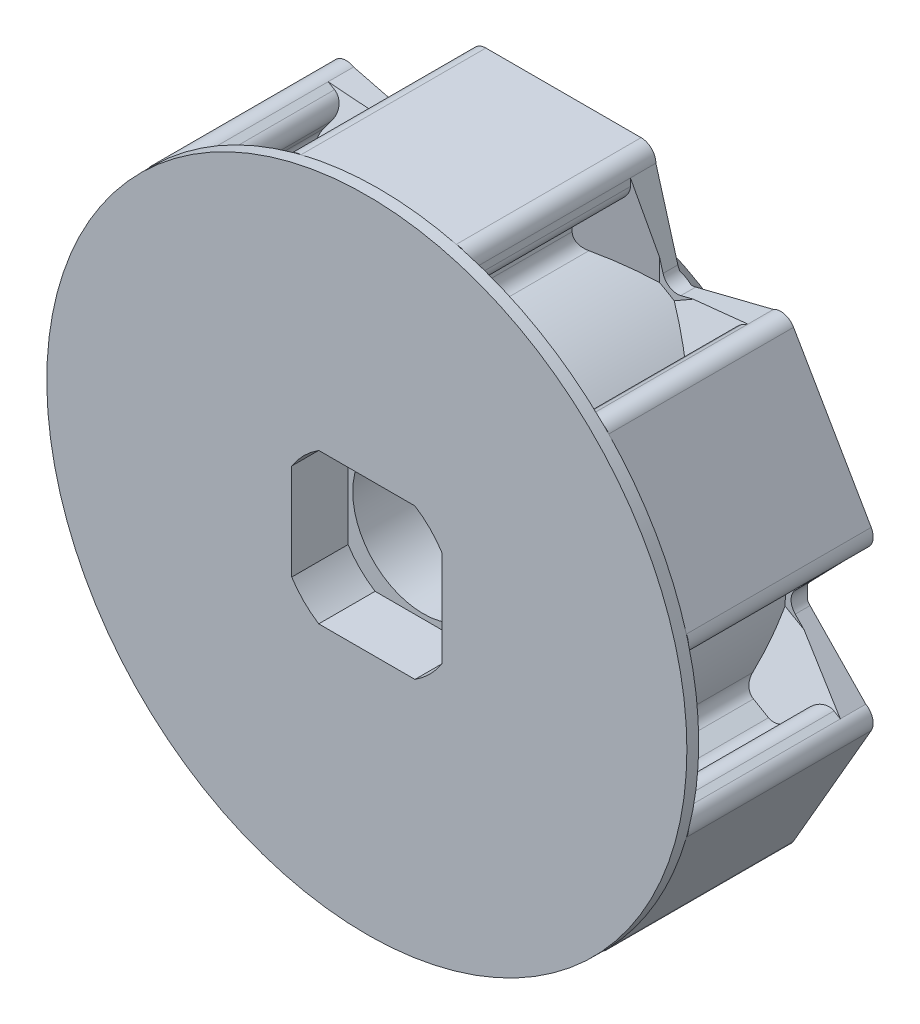
SolidWorks part; units mm, degrees
material "PE High Density"
ref_plane "Front Plane" through (0, 0, 0) normal (0, 0, 1) x (1, 0, 0)
ref_plane "Top Plane" through (0, 0, 0) normal (0, 1, 0) x (1, 0, 0)
ref_plane "Right Plane" through (0, 0, 0) normal (1, 0, 0) x (0, 0, -1)
sketch "Sketch1" plane through (0, 0, 0) normal (0, 0, 1) x (1, 0, 0)
  circle A0 centre (0, 0) radius 32
  circle A1 centre (0, 0) radius 9.525
  circle A2 centre (0, 0) radius 50 construction
  dimension "D1" = 64
  dimension "D2" = 19.05
  dimension "D3" = 100
extrude "Boss-Extrude1" add sketch "Sketch1" along normal blind 23
sketch "Sketch3" plane through (0, 0, 0) normal (0, 0, -1) x (-1, 0, 0)
  line L1 (-12.5, 42) -> (12.5, 42)
  line L2 (-12.5, 42) -> (-12.5, 37)
  line L3 (-12.5, 37) -> (12.5, 37)
  line L4 (12.5, 42) -> (12.5, 37)
  line L5 (-12.5, 42) -> (12.5, 37) construction
  line L6 (-12.5, 37) -> (12.5, 42) construction
  line L7 (7.5, 31.1087) -> (-7.5, 31.1087)
  line L8 (7.5, 31.1087) -> (7.5, 37)
  line L9 (7.5, 37) -> (-7.5, 37)
  line L10 (-7.5, 31.1087) -> (-7.5, 37)
  line L11 (7.5, 31.1087) -> (-7.5, 37) construction
  line L12 (7.5, 37) -> (-7.5, 31.1087) construction
  circle A0 centre (0, 0) radius 32 construction
  circle A1 centre (0, 0) radius 50 construction
  point P0 (0, 39.5)
  point P5 (0, 34.0543)
  dimension "D1" = 100
  dimension "D2" = 15
  dimension "D3" = 25
  dimension "D4" = 5
  dimension "D5" = 42
extrude "Boss-Extrude2" add sketch "Sketch3" against normal up to surface (23 mm away) contours L2 L1 L4 L3 | L8 L7 L10 L9 up to face at (32, 0, 23)
fillet "Fillet1" radius 2 8 edges at (7.5, 31.1087, 11.5) (7.5, 37, 11.5) (12.5, 37, 11.5) (12.5, 42, 11.5) (-12.5, 42, 11.5) (-12.5, 37, 11.5) (-7.5, 37, 11.5) (-7.5, 31.1087, 11.5)
sketch "Sketch5" plane through (0, 42, 0) normal (0, 1, 0) x (1, 0, 0)
  line L0 (10.5, 0) -> (-10.5, 0) construction
  circle A0 centre (0, -11.9253) radius 2.5
  dimension "D1" = 5
  dimension "D2" = 11.9253
pattern_circular "CirPattern1" count 6 over 360 about axis through (0, 0, 0) along (0, 0, 1) of "Boss-Extrude2", "Fillet1"
sketch "Sketch2" plane through (0, 0, 23) normal (0, 0, 1) x (1, 0, 0)
  line L1 (-10.16, -10.16) -> (10.16, -10.16)
  line L2 (-10.16, -10.16) -> (-10.16, 10.16)
  line L3 (-10.16, 10.16) -> (10.16, 10.16)
  line L4 (10.16, -10.16) -> (10.16, 10.16)
  line L5 (-10.16, -10.16) -> (10.16, 10.16) construction
  line L6 (-10.16, 10.16) -> (10.16, -10.16) construction
  arc A0 (6.5068, 10.16) -> (10.16, 6.5068) centre (0, 0) cw
  arc A1 (-6.5068, 10.16) -> (-10.16, 6.5068) centre (0, 0) ccw
  arc A2 (-10.16, -6.5068) -> (-6.5068, -10.16) centre (0, 0) ccw
  arc A3 (6.5068, -10.16) -> (10.16, -6.5068) centre (0, 0) ccw
  point P0 (0, 0)
  dimension "D1" = 20.32
extrude "Cut-Extrude2" cut sketch "Sketch2" against normal blind 6.02 contours L1 A3 L4 A0 L3 A1 L2 A2
sketch "Sketch7" plane through (0, 0, 23) normal (0, 0, 1) x (1, 0, 0)
  line L35 (36.7929, 10.2728) -> (37.2929, 9.4067)
  line L37 (36.7929, 10.2728) -> (37.2929, 9.4067)
  line L39 (40.025, 8.6747) -> (40.891, 9.1747)
  line L41 (40.025, 8.6747) -> (40.891, 9.1747)
  line L43 (41.6231, 11.9067) -> (31.1231, 30.0933)
  line L45 (41.6231, 11.9067) -> (31.1231, 30.0933)
  line L47 (28.391, 30.8253) -> (27.525, 30.3253)
  line L48 (7.5, 32.6458) -> (7.5, 35)
  line L49 (9.5, 37) -> (10.5, 37)
  line L50 (12.5, 39) -> (12.5, 40)
  line L51 (10.5, 42) -> (-10.5, 42)
  line L52 (-12.5, 40) -> (-12.5, 39)
  line L53 (-10.5, 37) -> (-9.5, 37)
  line L54 (-7.5, 35) -> (-7.5, 32.6458)
  line L56 (28.391, 30.8253) -> (27.525, 30.3253)
  line L58 (26.7929, 27.5933) -> (27.2929, 26.7272)
  line L60 (26.7929, 27.5933) -> (27.2929, 26.7272)
  line L62 (26.5609, 23.9952) -> (24.5221, 22.8181)
  line L64 (26.5609, 23.9952) -> (24.5221, 22.8181)
  line L66 (-24.5221, 22.8181) -> (-26.5609, 23.9952)
  line L68 (-24.5221, 22.8181) -> (-26.5609, 23.9952)
  line L70 (-27.2929, 26.7272) -> (-26.7929, 27.5933)
  line L72 (-27.2929, 26.7272) -> (-26.7929, 27.5933)
  line L74 (-27.525, 30.3253) -> (-28.391, 30.8253)
  line L76 (-27.525, 30.3253) -> (-28.391, 30.8253)
  line L78 (-31.1231, 30.0933) -> (-41.6231, 11.9067)
  line L80 (-31.1231, 30.0933) -> (-41.6231, 11.9067)
  line L82 (-40.891, 9.1747) -> (-40.025, 8.6747)
  line L90 (7.5, 32.6458) -> (7.5, 35)
  line L91 (9.5, 37) -> (10.5, 37)
  line L92 (12.5, 39) -> (12.5, 40)
  line L93 (10.5, 42) -> (-10.5, 42)
  line L94 (-12.5, 40) -> (-12.5, 39)
  line L95 (-10.5, 37) -> (-9.5, 37)
  line L96 (-7.5, 35) -> (-7.5, 32.6458)
  line L126 (-40.891, 9.1747) -> (-40.025, 8.6747)
  line L128 (-37.2929, 9.4067) -> (-36.7929, 10.2728)
  line L130 (-37.2929, 9.4067) -> (-36.7929, 10.2728)
  line L132 (-34.0609, 11.0048) -> (-32.0221, 9.8277)
  line L134 (-34.0609, 11.0048) -> (-32.0221, 9.8277)
  line L136 (-32.0221, -9.8277) -> (-34.0609, -11.0048)
  line L138 (-32.0221, -9.8277) -> (-34.0609, -11.0048)
  line L147 (-36.7929, -10.2728) -> (-37.2929, -9.4067)
  line L148 (-36.7929, -10.2728) -> (-37.2929, -9.4067)
  line L149 (-40.025, -8.6747) -> (-40.891, -9.1747)
  line L150 (-40.025, -8.6747) -> (-40.891, -9.1747)
  line L151 (-41.6231, -11.9067) -> (-31.1231, -30.0933)
  line L152 (-41.6231, -11.9067) -> (-31.1231, -30.0933)
  line L153 (-28.391, -30.8253) -> (-27.525, -30.3253)
  line L154 (-28.391, -30.8253) -> (-27.525, -30.3253)
  line L155 (-26.7929, -27.5933) -> (-27.2929, -26.7272)
  line L156 (-26.7929, -27.5933) -> (-27.2929, -26.7272)
  line L157 (-26.5609, -23.9952) -> (-24.5221, -22.8181)
  line L158 (-26.5609, -23.9952) -> (-24.5221, -22.8181)
  line L159 (-7.5, -32.6458) -> (-7.5, -35)
  line L160 (-7.5, -32.6458) -> (-7.5, -35)
  line L161 (-9.5, -37) -> (-10.5, -37)
  line L162 (-9.5, -37) -> (-10.5, -37)
  line L163 (-12.5, -39) -> (-12.5, -40)
  line L164 (-12.5, -39) -> (-12.5, -40)
  line L165 (-10.5, -42) -> (10.5, -42)
  line L166 (-10.5, -42) -> (10.5, -42)
  line L167 (12.5, -40) -> (12.5, -39)
  line L168 (12.5, -40) -> (12.5, -39)
  line L169 (10.5, -37) -> (9.5, -37)
  line L170 (10.5, -37) -> (9.5, -37)
  line L171 (7.5, -35) -> (7.5, -32.6458)
  line L172 (7.5, -35) -> (7.5, -32.6458)
  line L173 (24.5221, -22.8181) -> (26.5609, -23.9952)
  line L174 (24.5221, -22.8181) -> (26.5609, -23.9952)
  line L175 (27.2929, -26.7272) -> (26.7929, -27.5933)
  line L176 (27.2929, -26.7272) -> (26.7929, -27.5933)
  line L177 (27.525, -30.3253) -> (28.391, -30.8253)
  line L178 (27.525, -30.3253) -> (28.391, -30.8253)
  line L179 (31.1231, -30.0933) -> (41.6231, -11.9067)
  line L180 (31.1231, -30.0933) -> (41.6231, -11.9067)
  line L181 (40.891, -9.1747) -> (40.025, -8.6747)
  line L182 (40.891, -9.1747) -> (40.025, -8.6747)
  line L183 (37.2929, -9.4067) -> (36.7929, -10.2728)
  line L184 (37.2929, -9.4067) -> (36.7929, -10.2728)
  line L185 (34.0609, -11.0048) -> (32.0221, -9.8277)
  line L186 (34.0609, -11.0048) -> (32.0221, -9.8277)
  line L187 (32.0221, 9.8277) -> (34.0609, 11.0048)
  line L188 (32.0221, 9.8277) -> (34.0609, 11.0048)
  circle A0 centre (0, 0) radius 50
  arc A46 (37.2929, 9.4067) -> (40.025, 8.6747) centre (39.025, 10.4067) ccw
  arc A48 (37.2929, 9.4067) -> (40.025, 8.6747) centre (39.025, 10.4067) ccw
  arc A50 (40.891, 9.1747) -> (41.6231, 11.9067) centre (39.891, 10.9067) ccw
  arc A52 (40.891, 9.1747) -> (41.6231, 11.9067) centre (39.891, 10.9067) ccw
  arc A54 (31.1231, 30.0933) -> (28.391, 30.8253) centre (29.391, 29.0933) ccw
  arc A56 (31.1231, 30.0933) -> (28.391, 30.8253) centre (29.391, 29.0933) ccw
  arc A58 (27.525, 30.3253) -> (26.7929, 27.5933) centre (28.525, 28.5933) ccw
  arc A60 (22.1385, 23.106) -> (8.9412, 30.7255) centre (0, 0) ccw
  arc A61 (7.5, 32.6458) -> (8.9412, 30.7255) centre (9.5, 32.6458) ccw
  arc A62 (9.5, 37) -> (7.5, 35) centre (9.5, 35) ccw
  arc A63 (10.5, 37) -> (12.5, 39) centre (10.5, 39) ccw
  arc A64 (12.5, 40) -> (10.5, 42) centre (10.5, 40) ccw
  arc A65 (-10.5, 42) -> (-12.5, 40) centre (-10.5, 40) ccw
  arc A66 (-12.5, 39) -> (-10.5, 37) centre (-10.5, 39) ccw
  arc A67 (-7.5, 35) -> (-9.5, 37) centre (-9.5, 35) ccw
  arc A68 (-8.9412, 30.7255) -> (-7.5, 32.6458) centre (-9.5, 32.6458) ccw
  arc A69 (-8.9412, 30.7255) -> (-22.1385, 23.106) centre (0, 0) ccw
  arc A70 (27.525, 30.3253) -> (26.7929, 27.5933) centre (28.525, 28.5933) ccw
  arc A72 (26.5609, 23.9952) -> (27.2929, 26.7272) centre (25.5609, 25.7272) ccw
  arc A74 (26.5609, 23.9952) -> (27.2929, 26.7272) centre (25.5609, 25.7272) ccw
  arc A76 (22.1385, 23.106) -> (24.5221, 22.8181) centre (23.5221, 24.5502) ccw
  arc A78 (22.1385, 23.106) -> (24.5221, 22.8181) centre (23.5221, 24.5502) ccw
  arc A80 (-24.5221, 22.8181) -> (-22.1385, 23.106) centre (-23.5221, 24.5502) ccw
  arc A82 (-24.5221, 22.8181) -> (-22.1385, 23.106) centre (-23.5221, 24.5502) ccw
  arc A84 (-27.2929, 26.7272) -> (-26.5609, 23.9952) centre (-25.5609, 25.7272) ccw
  arc A86 (-27.2929, 26.7272) -> (-26.5609, 23.9952) centre (-25.5609, 25.7272) ccw
  arc A87 (-22.1385, -23.106) -> (-8.9412, -30.7255) centre (0, 0) ccw
  arc A89 (-26.7929, 27.5933) -> (-27.525, 30.3253) centre (-28.525, 28.5933) ccw
  arc A91 (-26.7929, 27.5933) -> (-27.525, 30.3253) centre (-28.525, 28.5933) ccw
  arc A93 (-28.391, 30.8253) -> (-31.1231, 30.0933) centre (-29.391, 29.0933) ccw
  arc A95 (-28.391, 30.8253) -> (-31.1231, 30.0933) centre (-29.391, 29.0933) ccw
  arc A96 (8.9412, -30.7255) -> (22.1385, -23.106) centre (0, 0) ccw
  arc A98 (-41.6231, 11.9067) -> (-40.891, 9.1747) centre (-39.891, 10.9067) ccw
  arc A100 (-41.6231, 11.9067) -> (-40.891, 9.1747) centre (-39.891, 10.9067) ccw
  arc A102 (-40.025, 8.6747) -> (-37.2929, 9.4067) centre (-39.025, 10.4067) ccw
  arc A104 (-40.025, 8.6747) -> (-37.2929, 9.4067) centre (-39.025, 10.4067) ccw
  arc A105 (31.0796, -7.6195) -> (31.0796, 7.6195) centre (0, 0) ccw
  arc A107 (-34.0609, 11.0048) -> (-36.7929, 10.2728) centre (-35.0609, 9.2728) ccw
  arc A114 (22.1385, 23.106) -> (8.9412, 30.7255) centre (0, 0) ccw
  arc A115 (7.5, 32.6458) -> (8.9412, 30.7255) centre (9.5, 32.6458) ccw
  arc A116 (9.5, 37) -> (7.5, 35) centre (9.5, 35) ccw
  arc A117 (10.5, 37) -> (12.5, 39) centre (10.5, 39) ccw
  arc A118 (12.5, 40) -> (10.5, 42) centre (10.5, 40) ccw
  arc A119 (-10.5, 42) -> (-12.5, 40) centre (-10.5, 40) ccw
  arc A120 (-12.5, 39) -> (-10.5, 37) centre (-10.5, 39) ccw
  arc A121 (-7.5, 35) -> (-9.5, 37) centre (-9.5, 35) ccw
  arc A122 (-8.9412, 30.7255) -> (-7.5, 32.6458) centre (-9.5, 32.6458) ccw
  arc A123 (-8.9412, 30.7255) -> (-22.1385, 23.106) centre (0, 0) ccw
  arc A141 (-22.1385, -23.106) -> (-8.9412, -30.7255) centre (0, 0) ccw
  arc A150 (8.9412, -30.7255) -> (22.1385, -23.106) centre (0, 0) ccw
  arc A159 (31.0796, -7.6195) -> (31.0796, 7.6195) centre (0, 0) ccw
  arc A163 (-34.0609, 11.0048) -> (-36.7929, 10.2728) centre (-35.0609, 9.2728) ccw
  arc A165 (-31.0796, 7.6195) -> (-32.0221, 9.8277) centre (-33.0221, 8.0957) ccw
  arc A167 (-31.0796, 7.6195) -> (-32.0221, 9.8277) centre (-33.0221, 8.0957) ccw
  arc A169 (-31.0796, 7.6195) -> (-31.0796, -7.6195) centre (0, 0) ccw
  arc A171 (-31.0796, 7.6195) -> (-31.0796, -7.6195) centre (0, 0) ccw
  arc A173 (-32.0221, -9.8277) -> (-31.0796, -7.6195) centre (-33.0221, -8.0957) ccw
  arc A175 (-32.0221, -9.8277) -> (-31.0796, -7.6195) centre (-33.0221, -8.0957) ccw
  arc A186 (-36.7929, -10.2728) -> (-34.0609, -11.0048) centre (-35.0609, -9.2728) ccw
  arc A187 (-36.7929, -10.2728) -> (-34.0609, -11.0048) centre (-35.0609, -9.2728) ccw
  arc A188 (-37.2929, -9.4067) -> (-40.025, -8.6747) centre (-39.025, -10.4067) ccw
  arc A189 (-37.2929, -9.4067) -> (-40.025, -8.6747) centre (-39.025, -10.4067) ccw
  arc A190 (-40.891, -9.1747) -> (-41.6231, -11.9067) centre (-39.891, -10.9067) ccw
  arc A191 (-40.891, -9.1747) -> (-41.6231, -11.9067) centre (-39.891, -10.9067) ccw
  arc A192 (-31.1231, -30.0933) -> (-28.391, -30.8253) centre (-29.391, -29.0933) ccw
  arc A193 (-31.1231, -30.0933) -> (-28.391, -30.8253) centre (-29.391, -29.0933) ccw
  arc A194 (-27.525, -30.3253) -> (-26.7929, -27.5933) centre (-28.525, -28.5933) ccw
  arc A195 (-27.525, -30.3253) -> (-26.7929, -27.5933) centre (-28.525, -28.5933) ccw
  arc A196 (-26.5609, -23.9952) -> (-27.2929, -26.7272) centre (-25.5609, -25.7272) ccw
  arc A197 (-26.5609, -23.9952) -> (-27.2929, -26.7272) centre (-25.5609, -25.7272) ccw
  arc A198 (-22.1385, -23.106) -> (-24.5221, -22.8181) centre (-23.5221, -24.5502) ccw
  arc A199 (-22.1385, -23.106) -> (-24.5221, -22.8181) centre (-23.5221, -24.5502) ccw
  arc A200 (-7.5, -32.6458) -> (-8.9412, -30.7255) centre (-9.5, -32.6458) ccw
  arc A201 (-7.5, -32.6458) -> (-8.9412, -30.7255) centre (-9.5, -32.6458) ccw
  arc A202 (-9.5, -37) -> (-7.5, -35) centre (-9.5, -35) ccw
  arc A203 (-9.5, -37) -> (-7.5, -35) centre (-9.5, -35) ccw
  arc A204 (-10.5, -37) -> (-12.5, -39) centre (-10.5, -39) ccw
  arc A205 (-10.5, -37) -> (-12.5, -39) centre (-10.5, -39) ccw
  arc A206 (-12.5, -40) -> (-10.5, -42) centre (-10.5, -40) ccw
  arc A207 (-12.5, -40) -> (-10.5, -42) centre (-10.5, -40) ccw
  arc A208 (10.5, -42) -> (12.5, -40) centre (10.5, -40) ccw
  arc A209 (10.5, -42) -> (12.5, -40) centre (10.5, -40) ccw
  arc A210 (12.5, -39) -> (10.5, -37) centre (10.5, -39) ccw
  arc A211 (12.5, -39) -> (10.5, -37) centre (10.5, -39) ccw
  arc A212 (7.5, -35) -> (9.5, -37) centre (9.5, -35) ccw
  arc A213 (7.5, -35) -> (9.5, -37) centre (9.5, -35) ccw
  arc A214 (8.9412, -30.7255) -> (7.5, -32.6458) centre (9.5, -32.6458) ccw
  arc A215 (8.9412, -30.7255) -> (7.5, -32.6458) centre (9.5, -32.6458) ccw
  arc A216 (24.5221, -22.8181) -> (22.1385, -23.106) centre (23.5221, -24.5502) ccw
  arc A217 (24.5221, -22.8181) -> (22.1385, -23.106) centre (23.5221, -24.5502) ccw
  arc A218 (27.2929, -26.7272) -> (26.5609, -23.9952) centre (25.5609, -25.7272) ccw
  arc A219 (27.2929, -26.7272) -> (26.5609, -23.9952) centre (25.5609, -25.7272) ccw
  arc A220 (26.7929, -27.5933) -> (27.525, -30.3253) centre (28.525, -28.5933) ccw
  arc A221 (26.7929, -27.5933) -> (27.525, -30.3253) centre (28.525, -28.5933) ccw
  arc A222 (28.391, -30.8253) -> (31.1231, -30.0933) centre (29.391, -29.0933) ccw
  arc A223 (28.391, -30.8253) -> (31.1231, -30.0933) centre (29.391, -29.0933) ccw
  arc A224 (41.6231, -11.9067) -> (40.891, -9.1747) centre (39.891, -10.9067) ccw
  arc A225 (41.6231, -11.9067) -> (40.891, -9.1747) centre (39.891, -10.9067) ccw
  arc A226 (40.025, -8.6747) -> (37.2929, -9.4067) centre (39.025, -10.4067) ccw
  arc A227 (40.025, -8.6747) -> (37.2929, -9.4067) centre (39.025, -10.4067) ccw
  arc A228 (34.0609, -11.0048) -> (36.7929, -10.2728) centre (35.0609, -9.2728) ccw
  arc A229 (34.0609, -11.0048) -> (36.7929, -10.2728) centre (35.0609, -9.2728) ccw
  arc A230 (31.0796, -7.6195) -> (32.0221, -9.8277) centre (33.0221, -8.0957) ccw
  arc A231 (31.0796, -7.6195) -> (32.0221, -9.8277) centre (33.0221, -8.0957) ccw
  arc A232 (32.0221, 9.8277) -> (31.0796, 7.6195) centre (33.0221, 8.0957) ccw
  arc A233 (32.0221, 9.8277) -> (31.0796, 7.6195) centre (33.0221, 8.0957) ccw
  arc A234 (36.7929, 10.2728) -> (34.0609, 11.0048) centre (35.0609, 9.2728) ccw
  arc A235 (36.7929, 10.2728) -> (34.0609, 11.0048) centre (35.0609, 9.2728) ccw
  dimension "D2" = 100
  dimension "D1" = 0
sketch "Sketch8" plane through (0, 0, 23) normal (0, 0, 1) x (1, 0, 0)
  line L36 (10.16, -6.5068) -> (10.16, 6.5068)
  line L37 (-6.5068, -10.16) -> (6.5068, -10.16)
  line L38 (-10.16, 6.5068) -> (-10.16, -6.5068)
  line L39 (6.5068, 10.16) -> (-6.5068, 10.16)
  line L40 (10.16, -6.5068) -> (10.16, 6.5068)
  line L41 (-6.5068, -10.16) -> (6.5068, -10.16)
  line L42 (-10.16, 6.5068) -> (-10.16, -6.5068)
  line L43 (6.5068, 10.16) -> (-6.5068, 10.16)
  circle A0 centre (0, 0) radius 43.2926
  arc A30 (10.16, 6.5068) -> (6.5068, 10.16) centre (0, 0) ccw
  arc A31 (6.5068, -10.16) -> (10.16, -6.5068) centre (0, 0) ccw
  arc A32 (-10.16, -6.5068) -> (-6.5068, -10.16) centre (0, 0) ccw
  arc A33 (-6.5068, 10.16) -> (-10.16, 6.5068) centre (0, 0) ccw
  arc A34 (10.16, 6.5068) -> (6.5068, 10.16) centre (0, 0) ccw
  arc A35 (6.5068, -10.16) -> (10.16, -6.5068) centre (0, 0) ccw
  arc A36 (-10.16, -6.5068) -> (-6.5068, -10.16) centre (0, 0) ccw
  arc A37 (-6.5068, 10.16) -> (-10.16, 6.5068) centre (0, 0) ccw
  dimension "D1" = 0
extrude "Boss-Extrude3" add sketch "Sketch8" along normal blind 1.6
sketch "Sketch10" plane through (0, 0, 0) normal (0, 0, -1) x (-1, 0, 0)
  line L2 (-12.5, 40) -> (-16, 27.7128)
  line L3 (-10.5, 42) -> (10.5, 42)
  line L4 (-10.5, 42) -> (10.5, 42)
  line L5 (12.5, 40) -> (16, 27.7128)
  line L6 (40.891, 9.1747) -> (32, 0)
  line L7 (31.1231, 30.0933) -> (41.6231, 11.9067)
  line L8 (28.391, 30.8253) -> (16, 27.7128)
  line L9 (28.391, -30.8253) -> (16, -27.7128)
  line L10 (41.6231, -11.9067) -> (31.1231, -30.0933)
  line L11 (40.891, -9.1747) -> (32, 0)
  line L12 (-12.5, -40) -> (-16, -27.7128)
  line L13 (10.5, -42) -> (-10.5, -42)
  line L14 (12.5, -40) -> (16, -27.7128)
  line L15 (-40.891, -9.1747) -> (-32, 0)
  line L16 (-31.1231, -30.0933) -> (-41.6231, -11.9067)
  line L17 (-28.391, -30.8253) -> (-16, -27.7128)
  line L18 (-28.391, 30.8253) -> (-16, 27.7128)
  line L19 (-41.6231, 11.9067) -> (-31.1231, 30.0933)
  line L20 (-40.891, 9.1747) -> (-32, 0)
  arc A2 (-10.5, 42) -> (-12.5, 40) centre (-10.5, 40) ccw
  arc A3 (-10.5, 42) -> (-12.5, 40) centre (-10.5, 40) ccw
  arc A4 (-8.9412, 30.7255) -> (-22.1385, 23.106) centre (0, 0) ccw construction
  arc A5 (12.5, 40) -> (10.5, 42) centre (10.5, 40) ccw
  arc A6 (12.5, 40) -> (10.5, 42) centre (10.5, 40) ccw
  arc A7 (22.1385, 23.106) -> (8.9412, 30.7255) centre (0, 0) ccw construction
  arc A8 (40.891, 9.1747) -> (41.6231, 11.9067) centre (39.891, 10.9067) ccw
  arc A9 (31.1231, 30.0933) -> (28.391, 30.8253) centre (29.391, 29.0933) ccw
  arc A10 (28.391, -30.8253) -> (31.1231, -30.0933) centre (29.391, -29.0933) ccw
  arc A11 (41.6231, -11.9067) -> (40.891, -9.1747) centre (39.891, -10.9067) ccw
  arc A12 (-12.5, -40) -> (-10.5, -42) centre (-10.5, -40) ccw
  arc A13 (10.5, -42) -> (12.5, -40) centre (10.5, -40) ccw
  arc A14 (-40.891, -9.1747) -> (-41.6231, -11.9067) centre (-39.891, -10.9067) ccw
  arc A15 (-31.1231, -30.0933) -> (-28.391, -30.8253) centre (-29.391, -29.0933) ccw
  arc A16 (-28.391, 30.8253) -> (-31.1231, 30.0933) centre (-29.391, 29.0933) ccw
  arc A17 (-41.6231, 11.9067) -> (-40.891, 9.1747) centre (-39.891, 10.9067) ccw
  circle A18 centre (0, 0) radius 9.525
  circle A19 centre (0, 0) radius 9.525
  point P57 (0, 0)
  dimension "D1" = 0
  dimension "D2" = 0
  dimension "D4" = 0
  dimension "D3" = 6
extrude "Boss-Extrude5" add sketch "Sketch10" along normal blind 2
chamfer "Chamfer2" distance 7.5 angle 30 2 edges at (7.5, 33.8229, 0) (-7.5, 33.8229, 0)
chamfer "Chamfer3" distance 7.5 angle 30 10 edges at (7.5, -33.8229, 0) (-25.5415, -23.4066, 0) (-33.0415, 10.4163, 0) (-25.5415, 23.4066, 0) (-33.0415, -10.4163, 0) (-7.5, -33.8229, 0) (25.5415, -23.4066, 0) (33.0415, -10.4163, 0) (33.0415, 10.4163, 0) (25.5415, 23.4066, 0)
fillet "Fillet2" radius 2 6 edges at (-16, -27.7128, -1) (-32, 0, -1) (-16, 27.7128, -1) (16, 27.7128, -1) (32, 0, -1) (16, -27.7128, -1)
sketch "Sketch11" plane through (0, 0, -2) normal (0, 0, -1) x (-1, 0, 0)
  circle A0 centre (0, 0) radius 27
  dimension "D1" = 54
extrude "Cut-Extrude3" cut sketch "Sketch11" against normal blind 9
chamfer "Chamfer4" distance 8 angle 30 1 edges at (-27, 0, 7)
sketch "Sketch12" plane through (0, 0, -2) normal (0, 0, -1) x (-1, 0, 0)
  circle A0 centre (0, 0) radius 27
  circle A1 centre (0, 0) radius 30
  dimension "D1" = 60
extrude "Boss-Extrude6" add sketch "Sketch12" along normal blind 3
chamfer "Chamfer5" distance 3 angle 45 1 edges at (-30, 0, -2)
